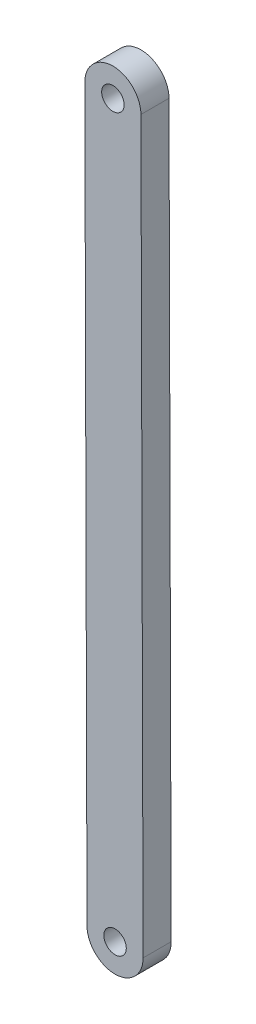
SolidWorks part; units mm, degrees
ref_plane "Front Plane" through (0, 0, 0) normal (0, 0, 1) x (1, 0, 0)
ref_plane "Top Plane" through (0, 0, 0) normal (0, 1, 0) x (1, 0, 0)
ref_plane "Right Plane" through (0, 0, 0) normal (1, 0, 0) x (0, 0, -1)
sketch "Sketch1" plane through (0, 0, 0) normal (0, 0, 1) x (1, 0, 0)
  line L0 (-16.1835, 155.9532) -> (-15.7958, 25.9538)
  line L1 (-25.7957, 25.924) -> (-26.1835, 155.9234)
  circle A0 centre (-20.7957, 25.9389) radius 2 construction
  circle A1 centre (-20.7957, 25.9389) radius 2
  circle A2 centre (-21.1835, 155.9383) radius 2 construction
  circle A3 centre (-21.1835, 155.9383) radius 2
  arc A4 (-15.7958, 25.9538) -> (-25.7957, 25.924) centre (-20.7957, 25.9389) cw
  arc A5 (-26.1835, 155.9234) -> (-16.1835, 155.9532) centre (-21.1835, 155.9383) cw
  dimension "D1" = 5
  dimension "D2" = 5
extrude "Boss-Extrude1" add sketch "Sketch1" along normal blind 5 from offset 5
